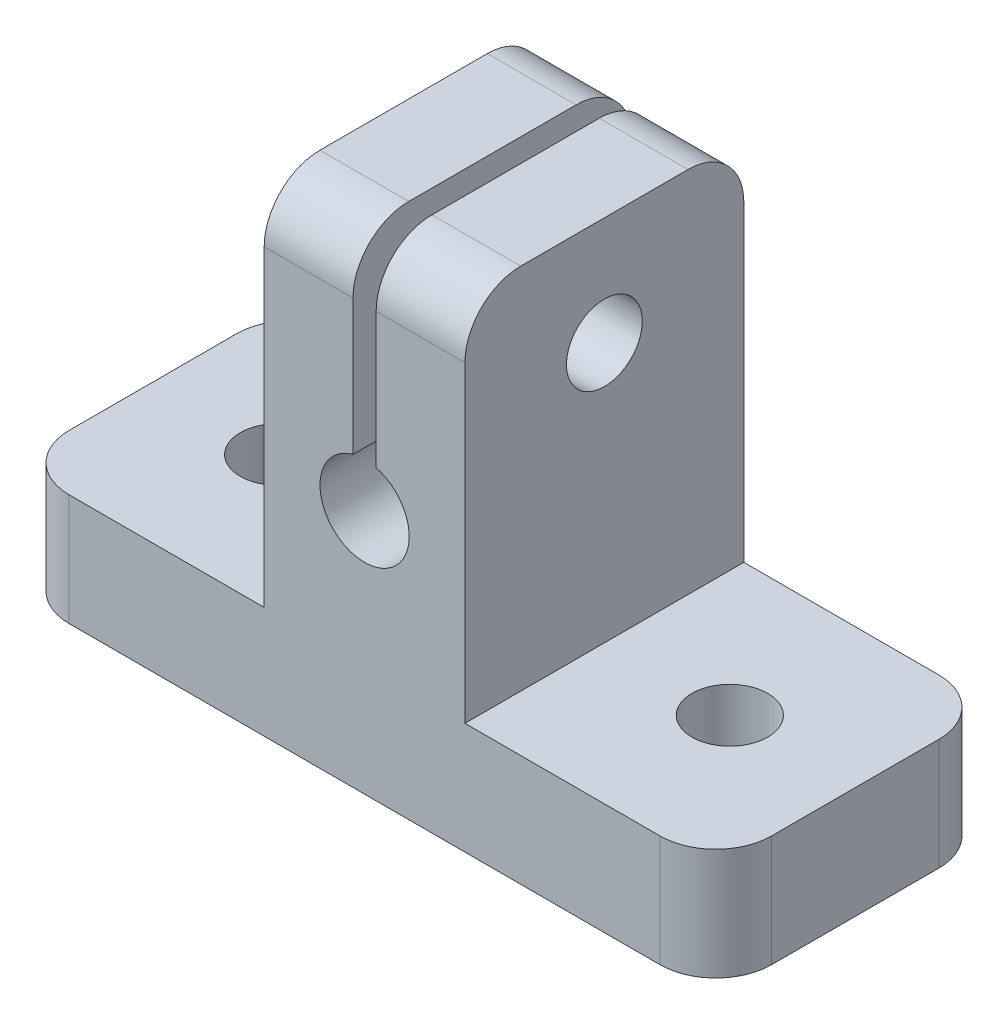
SolidWorks part; units mm, degrees
ref_plane "Front Plane" through (0, 0, 0) normal (0, 0, 1) x (1, 0, 0)
ref_plane "Top Plane" through (0, 0, 0) normal (0, 1, 0) x (1, 0, 0)
ref_plane "Right Plane" through (0, 0, 0) normal (1, 0, 0) x (0, 0, -1)
sketch "Sketch7" plane through (0, 0, 0) normal (0, 0, 1) x (1, 0, 0)
  line L0 (-42.3883, -20.8689) -> (-64.8745, -20.8689)
  line L1 (-33.3883, 12.1311) -> (-33.3883, -30.8689) construction
  line L2 (-24.3883, -20.8689) -> (-24.3883, 12.1311)
  line L3 (-24.3883, 12.1311) -> (-42.3883, 12.1311)
  line L4 (-42.3883, -20.8689) -> (-42.3883, 12.1311)
  line L7 (-1.9022, -30.8689) -> (-64.8745, -30.8689)
  line L8 (-1.9022, -30.8689) -> (-1.9022, -20.8689)
  line L9 (-1.9022, -20.8689) -> (-24.3883, -20.8689)
  line L10 (-64.8745, -30.8689) -> (-64.8745, -20.8689)
  dimension "D1" = 10
  dimension "D2" = 33
  dimension "D3" = 18
  dimension "D4" = 22.4861
extrude "Boss-Extrude3" add sketch "Sketch7" along normal blind 25
sketch "Sketch9" plane through (0, 0, 25) normal (0, 0, 1) x (1, 0, 0)
  line L1 (-33.3883, 12.1311) -> (-33.3883, -30.8689) construction
  line L2 (-24.3883, 12.1311) -> (-42.3883, 12.1311) construction
  line L3 (-64.8745, -30.8689) -> (-1.9022, -30.8689) construction
  circle A0 centre (-33.3883, -8.8689) radius 4
  dimension "D1" = 8
  dimension "D2" = 22
extrude "Cut-Extrude1" cut sketch "Sketch9" against normal up to surface (25 mm away) up to face at (-33.3883, -15.1189, 0)
sketch "Sketch10" plane through (0, -20.8689, 0) normal (0, 1, 0) x (-1, 0, 0)
  line L0 (13.1453, 0) -> (13.1453, 25) construction
  line L1 (1.9022, 0) -> (24.3883, 0) construction
  line L2 (1.9022, 25) -> (24.3883, 25) construction
  line L3 (24.3883, 12.5) -> (1.9022, 12.5) construction
  line L4 (24.3883, 25) -> (24.3883, 0) construction
  line L5 (1.9022, 25) -> (1.9022, 0) construction
  line L6 (53.6314, 0) -> (53.6314, 25) construction
  line L7 (42.3883, 0) -> (64.8745, 0) construction
  line L8 (42.3883, 25) -> (64.8745, 25) construction
  line L9 (64.8745, 12.5) -> (42.3883, 12.5) construction
  line L10 (64.8745, 25) -> (64.8745, 0) construction
  line L11 (42.3883, 25) -> (42.3883, 0) construction
  circle A0 centre (53.6314, 12.5) radius 3.4
  circle A1 centre (13.1453, 12.5) radius 3.4
  dimension "D1" = 6.8
  dimension "D2" = 6.8
extrude "Cut-Extrude2" cut sketch "Sketch10" against normal up to surface (10 mm away) up to face at (-33.3883, -30.8689, 12.5)
sketch "Sketch11" plane through (0, 0, 0) normal (0, 0, 1) x (1, 0, 0)
  line L0 (-33.3883, 12.1311) -> (-33.3883, -12.8689) construction
  line L1 (-24.3883, 12.1311) -> (-42.3883, 12.1311) construction
  line L2 (-34.427, -5.0061) -> (-34.427, 12.1311)
  line L3 (-34.427, -5.0061) -> (-32.3497, -5.0061)
  line L4 (-34.427, 12.1311) -> (-32.3497, 12.1311)
  line L5 (-32.3497, -5.0061) -> (-32.3497, 12.1311)
  line L6 (-34.427, -5.0061) -> (-32.3497, 12.1311) construction
  line L7 (-34.427, 12.1311) -> (-32.3497, -5.0061) construction
  circle A0 centre (-33.3883, -8.8689) radius 4 construction
  point P6 (-34.8883, -6.0694)
  point P9 (-33.3883, 3.5625)
extrude "Cut-Extrude3" cut sketch "Sketch11" along normal up to surface (25 mm away) up to face at (-29.3883, -8.8689, 25)
sketch "Sketch12" plane through (-42.3883, 0, 0) normal (-1, 0, 0) x (0, 0, 1)
  line L0 (12.5, 12.1311) -> (12.5, -30.8689) construction
  line L4 (25, 12.1311) -> (0, 12.1311) construction
  line L5 (25, -30.8689) -> (0, -30.8689) construction
  circle A0 centre (12.5, 2.4237) radius 3.4
  dimension "D1" = 6.8
extrude "Cut-Extrude4" cut sketch "Sketch12" against normal up to surface (18 mm away) up to face at (-24.3883, -4.3689, 12.5)
fillet "Fillet1" radius 5 8 edges at (-28.369, 12.1311, 0) (-38.4076, 12.1311, 0) (-28.369, 12.1311, 25) (-38.4076, 12.1311, 25) (-1.9022, -25.8689, 25) (-1.9022, -25.8689, 0) (-64.8745, -25.8689, 25) (-64.8745, -25.8689, 0)
